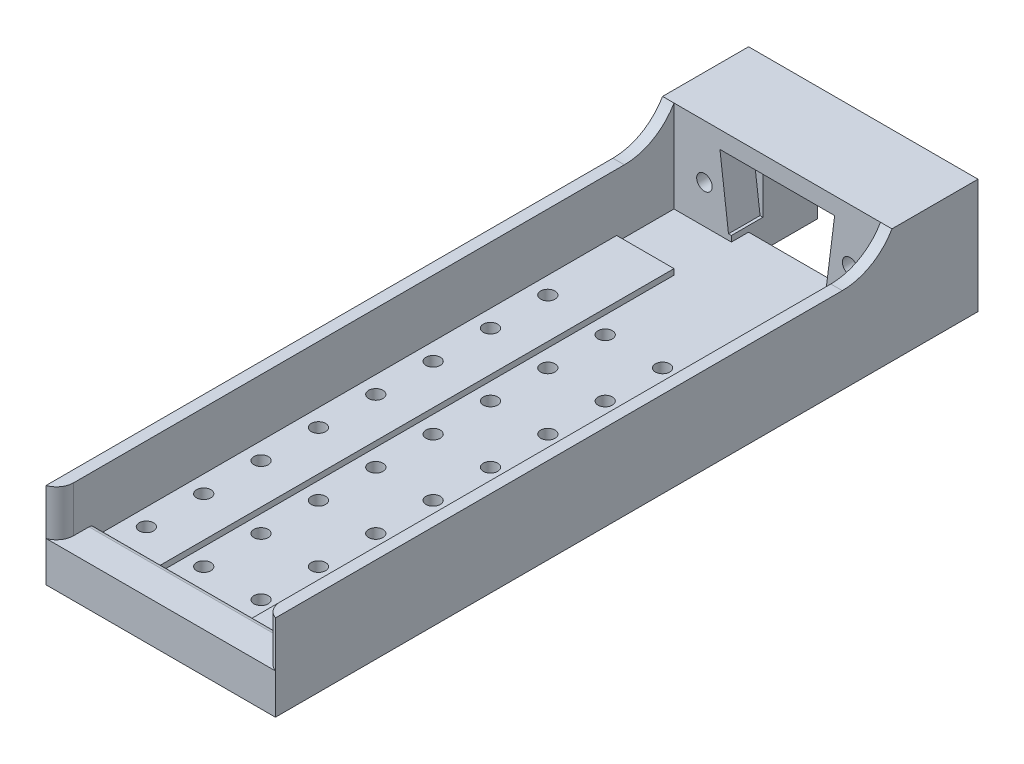
SolidWorks part; units mm, degrees
ref_plane "Front Plane" through (0, 0, 0) normal (0, 0, 1) x (1, 0, 0)
ref_plane "Top Plane" through (0, 0, 0) normal (0, 1, 0) x (1, 0, 0)
ref_plane "Right Plane" through (0, 0, 0) normal (1, 0, 0) x (0, 0, -1)
sketch "Esquisse1" plane through (0, 0, 0) normal (0, 0, 1) x (1, 0, 0)
  line L0 (18, 15) -> (20, 15)
  line L1 (20, 15) -> (20, 0)
  line L2 (20, 0) -> (-20, 0)
  line L3 (-20, 0) -> (-20, 15)
  line L4 (-20, 15) -> (-18, 15)
  line L5 (-18, 15) -> (-18, 5)
  line L6 (-18, 5) -> (-8, 5)
  line L7 (18, 5) -> (18, 15)
  line L8 (-8, 5) -> (-8, 4)
  line L9 (-8, 4) -> (8, 4)
  line L10 (8, 4) -> (8, 5)
  line L11 (8, 5) -> (18, 5)
  point P14 (0, 0)
  dimension "D1" = 2
  dimension "D2" = 1
  dimension "D3" = 36
  dimension "D4" = 10
  dimension "D5" = 2
  dimension "D6" = 40
  dimension "D7" = 5
  dimension "D8" = 10
  dimension "D9" = 4
extrude "Main" add sketch "Esquisse1" along normal mid plane 122.5
fillet "Front Conge" radius 3 2 edges at (18, 10, 61.25) (-18, 10, 61.25)
ref_plane "PlaneForDSub" through (0, 0, -46.25) normal (0, 0, 1) x (1, 0, 0)
sketch "Esquisse11" plane through (0, 0, -46.25) normal (0, 0, -1) x (-1, 0, 0)
  line L0 (20, 15) -> (20, 0) construction
  line L1 (-20, 20) -> (-18, 20)
  line L2 (-20, 20) -> (-20, 5)
  line L3 (-20, 5) -> (-18, 5)
  line L4 (-18, 20) -> (-18, 5)
  line L5 (18, 20) -> (20, 20)
  line L6 (18, 20) -> (18, 5)
  line L7 (18, 5) -> (20, 5)
  line L8 (20, 20) -> (20, 5)
  line L9 (-20, 0) -> (-20, 5) construction
  dimension "D1" = 15
extrude "DSub-Extrusion Attachment" add sketch "Esquisse11" along normal blind 15
sketch "Esquisse12" plane through (0, 0, -46.25) normal (0, 0, -1) x (-1, 0, 0)
  line L1 (-20, 20) -> (20, 20)
  line L2 (-20, 20) -> (-20, 5)
  line L3 (-20, 5) -> (20, 5)
  line L4 (20, 20) -> (20, 5)
  line L6 (20, 5) -> (20, 0) construction
  line L7 (-8, 14.175) -> (8, 14.175)
  line L8 (-8, 14.175) -> (-8, 7.175)
  line L9 (-8, 7.175) -> (8, 7.175)
  line L10 (8, 14.175) -> (8, 7.175)
  line L11 (18, 15) -> (18, 5) construction
  line L12 (-18, 5) -> (-18, 15) construction
  line L13 (-20, 0) -> (-20, 5) construction
  circle A0 centre (-12.7, 10.675) radius 1.35
  circle A1 centre (12.7, 10.675) radius 1.35
  point P20 (0, 7.175)
  point P22 (-8, 10.675)
  point P27 (18, 10)
  dimension "D5" = 2.7
  dimension "D1" = 15
  dimension "D2" = 7
  dimension "D3" = 16
  dimension "D4" = 5.3
  dimension "D6" = 25.4
  dimension "D7" = 12.7
  dimension "D8" = 5.675
  dimension "D9" = 5.3
extrude "DSub-Extrusion" add sketch "Esquisse12" along normal blind 15
sketch "Esquisse13" plane through (0, 0, -46.25) normal (0, 0, 1) x (1, 0, 0)
  line L0 (-10, 17) -> (10, 17)
  line L2 (10, 17) -> (8.5, 5)
  line L3 (-20, 20) -> (20, 20) construction
  line L4 (8.5, 5) -> (-8.5, 5)
  line L5 (-8.5, 5) -> (-10, 17)
  line L6 (8, 5) -> (-8, 5) construction
  point P10 (0, 17)
  point P11 (0, 20)
  dimension "D1" = 17
  dimension "D2" = 20
  dimension "D4" = 12
extrude "DSub-Front Hole" cut sketch "Esquisse13" against normal blind 5.5
sketch "Esquisse14" plane through (0, 0, -61.25) normal (0, 0, -1) x (-1, 0, 0)
  circle A0 centre (-12.7, 10.675) radius 4.3
  circle A1 centre (12.7, 10.675) radius 4.3
  circle A2 centre (12.7, 10.675) radius 1.35 construction
  dimension "D1" = 8.6
extrude "Bottom Hole" cut sketch "Esquisse14" against normal blind 2
sketch "Sketch7" plane through (0, 5, 0) normal (0, 1, 0) x (1, 0, 0)
  line L0 (-18, -58.4216) -> (-18, 46.25) construction
  line L1 (-18, 36.25) -> (18, 36.25)
  line L2 (-18, 36.25) -> (-18, 46.25)
  line L3 (-18, 46.25) -> (18, 46.25)
  line L4 (18, 36.25) -> (18, 46.25)
  dimension "D1" = 10
extrude "DSubBottomHole" cut sketch "Sketch7" against normal up to surface (1 mm away) up to face at (0, 4, 0)
fillet "Congé4" radius 10 2 edges at (-19, 15, -46.25) (19, 15, -46.25)
sketch "Sketch4" plane through (-20, 0, 0) normal (-1, 0, 0) x (0, 0, 1)
  line L0 (-46.25, -3.85) -> (-46.25, 3.85) construction
  line L1 (54.75, 7) -> (61.25, 7)
  line L2 (54.75, 7) -> (54.75, 0)
  line L3 (54.75, 0) -> (61.25, 0)
  line L4 (61.25, 7) -> (61.25, 0)
  dimension "D1" = 101
  dimension "D2" = 7
extrude "BottomStop" add sketch "Sketch4" against normal up to surface (40 mm away) up to face at (20, 10.5485, -3.3228)
fillet "Fillet1" radius 1 2 edges at (0, 4, 54.75) (0, 7, 54.75)
sketch "Sketch5" plane through (0, 0, 0) normal (0, -1, 0) x (-1, 0, 0)
  line L0 (20, 61.25) -> (-20, 61.25) construction
  line L1 (8, 61.25) -> (-8, 61.25)
  line L2 (8, 61.25) -> (8, 49.25)
  line L3 (8, 49.25) -> (-8, 49.25)
  line L4 (-8, 61.25) -> (-8, 49.25)
  line L5 (0, 55) -> (0, -55) construction
  point P5 (0, 61.25)
  dimension "D1" = 16
  dimension "D2" = 12
extrude "Cut-Extrude1" cut sketch "Sketch5" against normal up to surface (14.175 mm away) up to face at (0, 14.175, -56.5)
sketch "Sketch6" plane through (0, 0, 0) normal (0, -1, 0) x (-1, 0, 0)
  line L0 (0, 11) -> (0, -11) construction
  line L1 (-20, -61.25) -> (20, -61.25) construction
  line L2 (-11, 0) -> (11, 0) construction
  circle A0 centre (15, -48.75) radius 1.25
  dimension "D1" = 2.5
  dimension "D2" = 15
  dimension "D3" = 48.75
  dimension "D4" = 12.5
extrude "FixHole" cut sketch "Sketch6" against normal through all
pattern_linear "LPattern1" count 8 spacing 10 along (0, 0, -1) count 4 spacing 10 along (1, 0, 0) of "FixHole"
